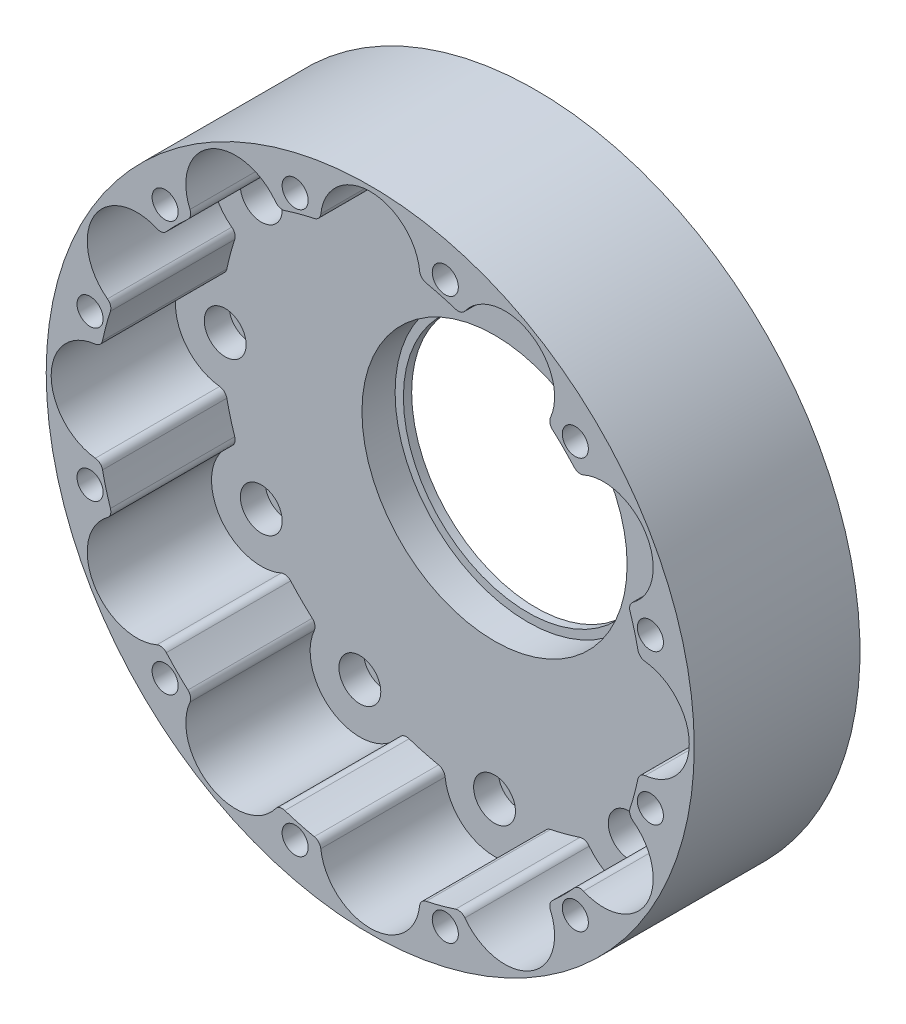
SolidWorks part; units mm, degrees
material "ABS"
ref_plane "Front Plane" through (0, 0, 0) normal (0, 0, 1) x (1, 0, 0)
ref_plane "Top Plane" through (0, 0, 0) normal (0, 1, 0) x (1, 0, 0)
ref_plane "Right Plane" through (0, 0, 0) normal (1, 0, 0) x (0, 0, -1)
sketch "Sketch1" plane through (0, 0, 0) normal (0, 0, 1) x (1, 0, 0)
  circle A0 centre (0, 0) radius 39.1
  circle A1 centre (0, 0) radius 32.5 construction
  circle A2 centre (32.5, 0) radius 2.525
  circle A3 centre (28.1458, -16.25) radius 2.525
  circle A4 centre (16.25, -28.1458) radius 2.525
  circle A5 centre (0, -32.5) radius 2.525
  circle A6 centre (-16.25, -28.1458) radius 2.525
  circle A7 centre (-28.1458, -16.25) radius 2.525
  circle A8 centre (-32.5, 0) radius 2.525
  circle A9 centre (-28.1458, 16.25) radius 2.525
  circle A10 centre (-16.25, 28.1458) radius 2.525
  circle A11 centre (0, 32.5) radius 2.525
  circle A12 centre (16.25, 28.1458) radius 2.525
  circle A13 centre (0, 0) radius 16
  circle A14 centre (28.1458, 16.25) radius 2.525
  point P28 (0, 0)
extrude "Boss-Extrude1" add sketch "Sketch1" along normal blind 3
sketch "Sketch2" plane through (0, 0, 0) normal (0, 0, -1) x (-1, 0, 0)
  circle A0 centre (0, 0) radius 16
  circle A1 centre (0, 0) radius 39.1
  circle A2 centre (0, 0) radius 39.1 construction
  dimension "D1" = 32
extrude "Boss-Extrude2" add sketch "Sketch2" along normal blind 2 contours A1 | A0
sketch "Sketch3" plane through (0, 0, 3) normal (0, 0, 1) x (1, 0, 0)
  circle A0 centre (32.5, 0) radius 1.6
  circle A1 centre (28.1458, -16.25) radius 1.6
  circle A2 centre (16.25, -28.1458) radius 1.6
  circle A3 centre (0, -32.5) radius 1.6
  circle A4 centre (-16.25, -28.1458) radius 1.6
  circle A5 centre (-28.1458, -16.25) radius 1.6
  circle A6 centre (-32.5, 0) radius 1.6
  circle A7 centre (-28.1458, 16.25) radius 1.6
  circle A8 centre (-16.25, 28.1458) radius 1.6
  circle A9 centre (0, 32.5) radius 1.6
  circle A10 centre (16.25, 28.1458) radius 1.6
  circle A11 centre (28.1458, 16.25) radius 1.6
  point P25 (0, 0)
  dimension "D1" = 3.2
  dimension "D2" = 12
sketch "Sketch4" plane through (0, 0, -2) normal (0, 0, -1) x (-1, 0, 0)
  circle A0 centre (0, 0) radius 16
  circle A1 centre (0, 0) radius 15
  dimension "D1" = 32
  dimension "D2" = 30
extrude "Boss-Extrude3" add sketch "Sketch4" against normal blind 1 contours A0
sketch "Sketch5" plane through (0, 0, 3) normal (0, 0, 1) x (1, 0, 0)
  circle A0 centre (0, 0) radius 39.1
  circle A1 centre (0, 0) radius 39.1 construction
  arc A2 (-11.029, 31.1024) -> (-21.421, 25.1026) centre (-16.25, 28.1458) ccw
  arc A3 (5.9998, 32.45) -> (-5.9998, 32.45) centre (0, 32.5) ccw
  arc A4 (21.421, 25.1026) -> (11.029, 31.1024) centre (16.25, 28.1458) ccw
  arc A5 (31.1024, 11.029) -> (25.1026, 21.421) centre (28.1458, 16.25) ccw
  arc A6 (32.45, -5.9998) -> (32.45, 5.9998) centre (32.5, 0) ccw
  arc A7 (25.1026, -21.421) -> (31.1024, -11.029) centre (28.1458, -16.25) ccw
  arc A8 (11.029, -31.1024) -> (21.421, -25.1026) centre (16.25, -28.1458) ccw
  arc A9 (-5.9998, -32.45) -> (5.9998, -32.45) centre (0, -32.5) ccw
  arc A10 (-21.421, -25.1026) -> (-11.029, -31.1024) centre (-16.25, -28.1458) ccw
  arc A11 (-31.1024, -11.029) -> (-25.1026, -21.421) centre (-28.1458, -16.25) ccw
  arc A12 (-32.45, 5.9998) -> (-32.45, -5.9998) centre (-32.5, 0) ccw
  arc A13 (-25.1026, -21.421) -> (-21.421, -25.1026) centre (0, 0) ccw
  arc A14 (-32.45, -5.9998) -> (-31.1024, -11.029) centre (0, 0) ccw
  arc A15 (-21.421, 25.1026) -> (-25.1026, 21.421) centre (0, 0) ccw
  arc A16 (-5.9998, 32.45) -> (-11.029, 31.1024) centre (0, 0) ccw
  arc A17 (11.029, 31.1024) -> (5.9998, 32.45) centre (0, 0) ccw
  arc A18 (25.1026, 21.421) -> (21.421, 25.1026) centre (0, 0) ccw
  arc A19 (32.45, 5.9998) -> (31.1024, 11.029) centre (0, 0) ccw
  arc A20 (31.1024, -11.029) -> (32.45, -5.9998) centre (0, 0) ccw
  arc A21 (21.421, -25.1026) -> (25.1026, -21.421) centre (0, 0) ccw
  arc A22 (5.9998, -32.45) -> (11.029, -31.1024) centre (0, 0) ccw
  arc A23 (-11.029, -31.1024) -> (-5.9998, -32.45) centre (0, 0) ccw
  arc A24 (-25.1026, 21.421) -> (-31.1024, 11.029) centre (-28.1458, 16.25) ccw
  arc A25 (-31.1024, 11.029) -> (-32.45, 5.9998) centre (0, 0) ccw
  point P30 (0, 0)
  dimension "D1" = 12
  dimension "D2" = 6
  dimension "D3" = 33
extrude "Boss-Extrude4" add sketch "Sketch5" along normal blind 15 contours A24 A15 A2 A0 | A16 A3 A0 A2 | A17 A4 A0 A3 | A18 A5 A0 A4 | A19 A6 A0 A5 | A20 A7 A0 A6 | A21 A8 A0 A7 | A22 A9 A0 A8 | A23 A10 A0 A9 | A13 A11 A0 A10 | A14 A12 A0 A11 | A24 A0 A12 A15
fillet "Fillet2" radius 1 24 edges at (11.029, -31.1024, 10.5) (5.9998, -32.45, 10.5) (32.45, -5.9998, 10.5) (31.1024, -11.029, 10.5) (25.1026, -21.421, 10.5) (21.421, -25.1026, 10.5) (-11.029, -31.1024, 10.5) (-5.9998, -32.45, 10.5) (-21.421, -25.1026, 10.5) (-25.1026, -21.421, 10.5) (-32.45, -5.9998, 10.5) (-31.1024, -11.029, 10.5) (-21.421, 25.1026, 10.5) (32.45, 5.9998, 10.5) (31.1024, 11.029, 10.5) (25.1026, 21.421, 10.5) (21.421, 25.1026, 10.5) (11.029, 31.1024, 10.5) (5.9998, 32.45, 10.5) (-5.9998, 32.45, 10.5) (-11.029, 31.1024, 10.5) (-32.45, 5.9998, 10.5) (-31.1024, 11.029, 10.5) (-25.1026, 21.421, 10.5)
sketch "Sketch7" plane through (0, 0, -2) normal (0, 0, -1) x (-1, 0, 0)
  line L0 (0, 0) -> (33.8074, -9.0587) construction
  line L1 (0, 0) -> (35, 0) construction
  circle A0 centre (33.8074, -9.0587) radius 1.575
  circle A1 centre (24.7487, -24.7487) radius 1.575
  circle A2 centre (9.0587, -33.8074) radius 1.575
  circle A3 centre (-9.0587, -33.8074) radius 1.575
  circle A4 centre (-24.7487, -24.7487) radius 1.575
  circle A5 centre (-33.8074, -9.0587) radius 1.575
  circle A6 centre (-33.8074, 9.0587) radius 1.575
  circle A7 centre (-24.7487, 24.7487) radius 1.575
  circle A8 centre (-9.0587, 33.8074) radius 1.575
  circle A9 centre (9.0587, 33.8074) radius 1.575
  circle A10 centre (24.7487, 24.7487) radius 1.575
  circle A11 centre (33.8074, 9.0587) radius 1.575
  point P26 (0, 0)
  dimension "D2" = 3.15
  dimension "D4" = 35
  dimension "D5" = 15
  dimension "D3" = 12
extrude "Cut-Extrude1" cut sketch "Sketch7" against normal through all
sketch "Sketch8" plane through (0, 0, -2) normal (0, 0, -1) x (-1, 0, 0)
  line L0 (27.5987, -26.3942) -> (27.5987, -23.1033)
  line L1 (37.0983, -9.0587) -> (35.4529, -6.2087)
  line L2 (35.4529, -6.2087) -> (32.162, -6.2087)
  line L3 (32.162, -6.2087) -> (30.5165, -9.0587)
  line L4 (30.5165, -9.0587) -> (32.162, -11.9087)
  line L5 (32.162, -11.9087) -> (35.4529, -11.9087)
  line L6 (35.4529, -11.9087) -> (37.0983, -9.0587)
  line L7 (27.5987, -23.1033) -> (24.7487, -21.4578)
  line L8 (24.7487, -21.4578) -> (21.8987, -23.1033)
  line L9 (21.8987, -23.1033) -> (21.8987, -26.3942)
  line L10 (21.8987, -26.3942) -> (24.7487, -28.0396)
  line L11 (24.7487, -28.0396) -> (27.5987, -26.3942)
  line L12 (10.7041, -36.6574) -> (12.3496, -33.8074)
  line L13 (12.3496, -33.8074) -> (10.7041, -30.9574)
  line L14 (10.7041, -30.9574) -> (7.4132, -30.9574)
  line L15 (7.4132, -30.9574) -> (5.7678, -33.8074)
  line L16 (5.7678, -33.8074) -> (7.4132, -36.6574)
  line L17 (7.4132, -36.6574) -> (10.7041, -36.6574)
  line L18 (-9.0587, -37.0983) -> (-6.2087, -35.4529)
  line L19 (-6.2087, -35.4529) -> (-6.2087, -32.162)
  line L20 (-6.2087, -32.162) -> (-9.0587, -30.5165)
  line L21 (-9.0587, -30.5165) -> (-11.9087, -32.162)
  line L22 (-11.9087, -32.162) -> (-11.9087, -35.4529)
  line L23 (-11.9087, -35.4529) -> (-9.0587, -37.0983)
  line L24 (-26.3942, -27.5987) -> (-23.1033, -27.5987)
  line L25 (-23.1033, -27.5987) -> (-21.4578, -24.7487)
  line L26 (-21.4578, -24.7487) -> (-23.1033, -21.8987)
  line L27 (-23.1033, -21.8987) -> (-26.3942, -21.8987)
  line L28 (-26.3942, -21.8987) -> (-28.0396, -24.7487)
  line L29 (-28.0396, -24.7487) -> (-26.3942, -27.5987)
  line L30 (-36.6574, -10.7041) -> (-33.8074, -12.3496)
  line L31 (-33.8074, -12.3496) -> (-30.9574, -10.7041)
  line L32 (-30.9574, -10.7041) -> (-30.9574, -7.4132)
  line L33 (-30.9574, -7.4132) -> (-33.8074, -5.7678)
  line L34 (-33.8074, -5.7678) -> (-36.6574, -7.4132)
  line L35 (-36.6574, -7.4132) -> (-36.6574, -10.7041)
  line L36 (-37.0983, 9.0587) -> (-35.4529, 6.2087)
  line L37 (-35.4529, 6.2087) -> (-32.162, 6.2087)
  line L38 (-32.162, 6.2087) -> (-30.5165, 9.0587)
  line L39 (-30.5165, 9.0587) -> (-32.162, 11.9087)
  line L40 (-32.162, 11.9087) -> (-35.4529, 11.9087)
  line L41 (-35.4529, 11.9087) -> (-37.0983, 9.0587)
  line L42 (-27.5987, 26.3942) -> (-27.5987, 23.1033)
  line L43 (-27.5987, 23.1033) -> (-24.7487, 21.4578)
  line L44 (-24.7487, 21.4578) -> (-21.8987, 23.1033)
  line L45 (-21.8987, 23.1033) -> (-21.8987, 26.3942)
  line L46 (-21.8987, 26.3942) -> (-24.7487, 28.0396)
  line L47 (-24.7487, 28.0396) -> (-27.5987, 26.3942)
  line L48 (-10.7041, 36.6574) -> (-12.3496, 33.8074)
  line L49 (-12.3496, 33.8074) -> (-10.7041, 30.9574)
  line L50 (-10.7041, 30.9574) -> (-7.4132, 30.9574)
  line L51 (-7.4132, 30.9574) -> (-5.7678, 33.8074)
  line L52 (-5.7678, 33.8074) -> (-7.4132, 36.6574)
  line L53 (-7.4132, 36.6574) -> (-10.7041, 36.6574)
  line L54 (9.0587, 37.0983) -> (6.2087, 35.4529)
  line L55 (6.2087, 35.4529) -> (6.2087, 32.162)
  line L56 (6.2087, 32.162) -> (9.0587, 30.5165)
  line L57 (9.0587, 30.5165) -> (11.9087, 32.162)
  line L58 (11.9087, 32.162) -> (11.9087, 35.4529)
  line L59 (11.9087, 35.4529) -> (9.0587, 37.0983)
  line L60 (26.3942, 27.5987) -> (23.1033, 27.5987)
  line L61 (23.1033, 27.5987) -> (21.4578, 24.7487)
  line L62 (21.4578, 24.7487) -> (23.1033, 21.8987)
  line L63 (23.1033, 21.8987) -> (26.3942, 21.8987)
  line L64 (26.3942, 21.8987) -> (28.0396, 24.7487)
  line L65 (28.0396, 24.7487) -> (26.3942, 27.5987)
  line L66 (36.6574, 10.7041) -> (33.8074, 12.3496)
  line L67 (33.8074, 12.3496) -> (30.9574, 10.7041)
  line L68 (30.9574, 10.7041) -> (30.9574, 7.4132)
  line L69 (30.9574, 7.4132) -> (33.8074, 5.7678)
  line L70 (33.8074, 5.7678) -> (36.6574, 7.4132)
  line L71 (36.6574, 7.4132) -> (36.6574, 10.7041)
  circle A0 centre (33.8074, -9.0587) radius 2.85 construction
  circle A1 centre (24.7487, -24.7487) radius 2.85 construction
  circle A2 centre (9.0587, -33.8074) radius 2.85 construction
  circle A3 centre (-9.0587, -33.8074) radius 2.85 construction
  circle A4 centre (-24.7487, -24.7487) radius 2.85 construction
  circle A5 centre (-33.8074, -9.0587) radius 2.85 construction
  circle A6 centre (-33.8074, 9.0587) radius 2.85 construction
  circle A7 centre (-24.7487, 24.7487) radius 2.85 construction
  circle A8 centre (-9.0587, 33.8074) radius 2.85 construction
  circle A9 centre (9.0587, 33.8074) radius 2.85 construction
  circle A10 centre (24.7487, 24.7487) radius 2.85 construction
  circle A11 centre (33.8074, 9.0587) radius 2.85 construction
  point P91 (0, 0)
  dimension "D1" = 5.7
  dimension "D2" = 12
extrude "Cut-Extrude3" cut sketch "Sketch8" against normal blind 3
sketch "Sketch9" plane through (0, 0, 3) normal (0, 0, 1) x (1, 0, 0)
  circle A0 centre (0, 0) radius 39.1
  circle A1 centre (0, 0) radius 38.5
  dimension "D1" = 77
equation "\"RingPinShaft\"= 5.05"
equation "\"CenterBearingOut\"=32.00"
equation "\"OutputBearingOut\"=50.00"
equation "\"RingPostIn\"=5.15"
equation "\"CamBearingOut\"=15.1"
equation "\"DiskOutputShaft\"=10.1"
equation "\"CenterShaft\"=25.2"
equation "\"Eccentricity\"=2"
equation "\"CycCamShaft\"=10.05"
equation "\"m3Thru\"=3.15"
equation "\"m3Insert\"=4.2"
equation "\"MountingHoleDiam\"=35"
equation "\"D2@Sketch7\"=\"m3Thru\""
equation "\"D4@Sketch7\"=\"MountingHoleDiam\""
